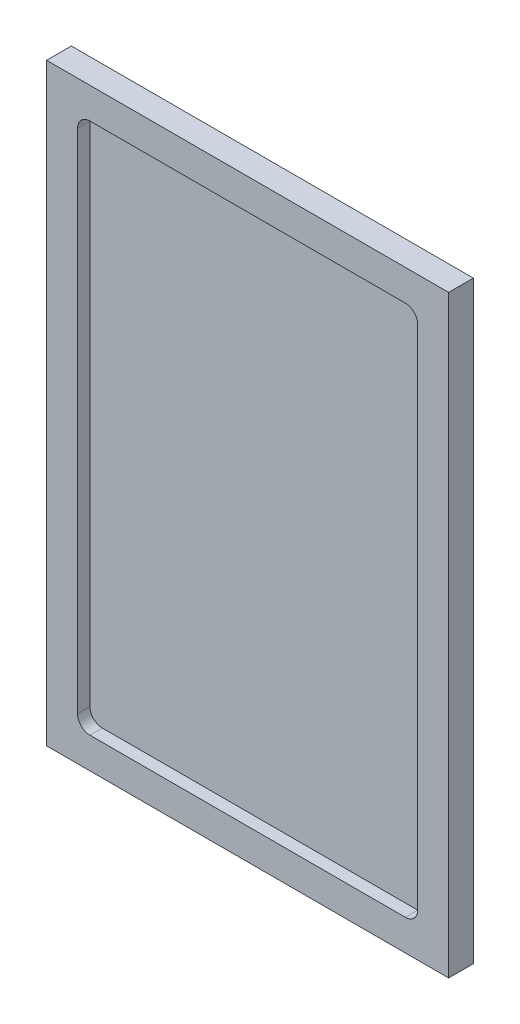
SolidWorks part; units mm, degrees
ref_plane "Front Plane" through (0, 0, 0) normal (0, 0, 1) x (1, 0, 0)
ref_plane "Top Plane" through (0, 0, 0) normal (0, 1, 0) x (1, 0, 0)
ref_plane "Right Plane" through (0, 0, 0) normal (1, 0, 0) x (0, 0, -1)
sketch "Sketch1" plane through (0, 0, 0) normal (0, 0, 1) x (1, 0, 0)
  line L1 (103.1875, -152.4) -> (-103.1875, -152.4)
  line L2 (103.1875, -152.4) -> (103.1875, 152.4)
  line L3 (103.1875, 152.4) -> (-103.1875, 152.4)
  line L4 (-103.1875, -152.4) -> (-103.1875, 152.4)
  line L5 (103.1875, -152.4) -> (-103.1875, 152.4) construction
  line L6 (103.1875, 152.4) -> (-103.1875, -152.4) construction
  point P0 (0, 0)
  dimension "D1" = 304.8
  dimension "D2" = 206.375
extrude "Boss-Extrude1" add sketch "Sketch1" along normal blind 12.7
sketch "Sketch2" plane through (0, 0, 12.7) normal (0, 0, 1) x (1, 0, 0)
  line L0 (-103.1875, 152.4) -> (-103.1875, -152.4) construction
  line L1 (80.9625, -136.525) -> (-80.9625, -136.525)
  line L2 (87.3125, -130.175) -> (87.3125, 130.175)
  line L3 (80.9625, 136.525) -> (-80.9625, 136.525)
  line L4 (-87.3125, -130.175) -> (-87.3125, 130.175)
  line L5 (87.3125, -136.525) -> (-87.3125, 136.525) construction
  line L6 (87.3125, 136.525) -> (-87.3125, -136.525) construction
  line L7 (103.1875, 152.4) -> (-103.1875, 152.4) construction
  arc A0 (-80.9625, -136.525) -> (-87.3125, -130.175) centre (-80.9625, -130.175) cw
  arc A1 (80.9625, -136.525) -> (87.3125, -130.175) centre (80.9625, -130.175) ccw
  arc A2 (87.3125, 130.175) -> (80.9625, 136.525) centre (80.9625, 130.175) ccw
  arc A3 (-80.9625, 136.525) -> (-87.3125, 130.175) centre (-80.9625, 130.175) ccw
  point P0 (0, 0)
  dimension "D3" = 6.35
  dimension "D1" = 15.875
  dimension "D2" = 15.875
extrude "Cut-Extrude1" cut sketch "Sketch2" against normal blind 6.35
